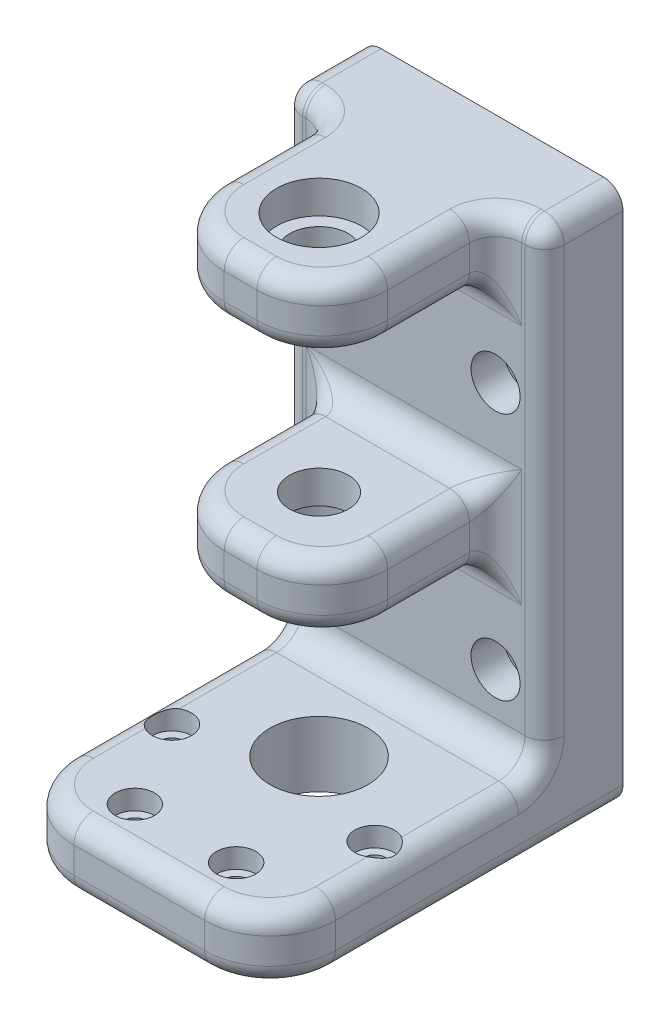
SolidWorks part; units mm, degrees
note: The reader was unsure of these and kept them because the rebuilt part matched: shared geometry of "Croquis3<2>".
ref_plane "Alzado" through (0, 0, 0) normal (1, 0, 0) x (0, 1, 0)
ref_plane "Planta" through (0, 0, 0) normal (0, 0, 1) x (0, 1, 0)
ref_plane "Vista lateral" through (0, 0, 0) normal (0, 1, 0) x (-1, 0, 0)
sketch "Croquis1" plane through (0, 0, 0) normal (0, 1, 0) x (-1, 0, 0)
  line L0 (-12.5, -14.5) -> (-20, -14.5)
  line L2 (-12.5, -14.5) -> (-12.5, 12)
  line L3 (-12.5, 12) -> (12.5, 12)
  line L4 (12.5, -14.5) -> (12.5, 12)
  line L7 (20, -14.5) -> (12.5, -14.5)
  line L8 (20, -14.5) -> (20, -26.5)
  line L9 (20, -26.5) -> (-20, -26.5)
  line L10 (-20, -14.5) -> (-20, -26.5)
  line L11 (0, 0) -> (0, -26.5) construction
  circle A0 centre (0, 0) radius 4.5
  circle A1 centre (0, 0) radius 4.05 construction
  point P0 (0, 0)
  point P16 (0, 12)
  dimension "D3" = 9
  dimension "D1" = 25
  dimension "D5" = 12
  dimension "D6" = 40
  dimension "D2" = 26.5
  dimension "D4" = 12
extrude "Saliente-Extruir1" add sketch "Croquis1" along normal mid plane 47
sketch "Croquis2" plane through (0, 0, 12) normal (0, 0, 1) x (1, 0, 0)
  line L0 (12.5, 23.5) -> (12.5, -23.5) construction
  line L1 (12.5, 13.5) -> (-12.5, 13.5)
  line L2 (12.5, 13.5) -> (12.5, -13.5)
  line L3 (12.5, -13.5) -> (-12.5, -13.5)
  line L4 (-12.5, 13.5) -> (-12.5, -13.5)
  line L5 (-12.5, 23.5) -> (-12.5, -23.5) construction
  line L8 (-12.5, -23.5) -> (12.5, -23.5) construction
  line L9 (-12.5, 23.5) -> (12.5, 23.5) construction
  dimension "D1" = 10
  dimension "D2" = 10
extrude "Cortar-Extruir1" cut sketch "Croquis2" against normal up to surface (26.5 mm away) up to face at (-16.25, 0, -14.5)
fillet "Redondeo1" radius 10 4 edges at (-12.5, 18.5, 12) (12.5, 18.5, 12) (-12.5, -18.5, 12) (12.5, -18.5, 12)
sketch "Croquis3" plane through (0, 0, 0) normal (0, 1, 0) x (-1, 0, 0)
  circle A0 centre (0, 0) radius 6.5
  dimension "D1" = 13
extrude "Cortar-Extruir2" cut sketch "Croquis3" along normal blind 5 from surface at -23.5 starting at face at (0, -23.5, -7.8858)
sketch "Croquis4" plane through (0, 0, -14.5) normal (0, 0, 1) x (0, 1, 0)
  line L0 (0, 12.5) -> (0, -12.5) construction
  line L2 (0, 12.5) -> (-38, 12.5) construction
  line L4 (-13.5, 12.5) -> (-23.5, 12.5) construction
  line L7 (-38, 12.5) -> (-38, -12.5) construction
  point P1 (0, -12.5)
  point P20 (-38, 12.5)
  point P23 (0, 12.5)
  point P37 (-38, -12.5)
  dimension "D1" = 0
  dimension "D3" = 38
extrude "Cortar-Extruir3" cut sketch "Croquis3<2>" against normal blind 5 from surface at 23.5 starting at face at (0, 23.5, -7.8858)
sketch "Croquis3<2>" plane through (0, 0, 0) normal (0, 1, 0) x (-1, 0, 0) same geometry as "Croquis3"
sketch "Croquis6" plane through (0, -23.5, 0) normal (0, -1, 0) x (1, 0, 0)
  line L1 (-20, -14.5) -> (20, -14.5)
  line L2 (-20, -14.5) -> (-20, -26.5)
  line L3 (-20, -26.5) -> (20, -26.5)
  line L4 (20, -14.5) -> (20, -26.5)
extrude "Saliente-Extruir2" add sketch "Croquis6" along normal blind 25
sketch "Croquis7" plane through (0, -48.5, 0) normal (0, -1, 0) x (1, 0, 0)
  line L0 (20, -26.5) -> (20, -14.5) construction
  line L1 (-20, -26.5) -> (20, -26.5)
  line L2 (-20, -26.5) -> (-20, 17.5)
  line L3 (-10, 27.5) -> (10, 27.5)
  line L4 (20, -26.5) -> (20, 17.5)
  line L5 (0, 7) -> (15.5, 7) construction
  line L6 (0, 7) -> (7.75, 20.4234) construction
  arc A0 (10, 27.5) -> (20, 17.5) centre (10, 17.5) cw
  arc A1 (-20, 17.5) -> (-10, 27.5) centre (-10, 17.5) cw
  circle A3 centre (0, 7) radius 15.5 construction
  circle A4 centre (0, 0) radius 7.5
  point P9 (20, 27.5)
  point P14 (0, 0)
  point P16 (15.5, 7)
  point P20 (7.75, 20.4234)
  point P21 (-7.75, 20.4234)
  point P22 (-15.5, 7)
  dimension "D2" = 10
  dimension "D3" = 7
  dimension "D4" = 31
  dimension "D7" = 15
  dimension "D1" = 54
  dimension "D6" = 60
  dimension "D5" = 4
extrude "Saliente-Extruir3" add sketch "Croquis7" along normal blind 10
sketch "Croquis8" plane through (0, -48.5, 0) normal (0, -1, 0) x (1, 0, 0)
  point P0 (15.5, 7)
  point P2 (7.75, 20.4234)
  point P4 (-7.75, 20.4234)
  point P6 (-15.5, 7)
hole_wizard "Refrentado para tornillo con cabeza troncocónica de M32" positions "Croquis8" profile "Croquis9" counterbore size "M3" standard "Ansi Metric" end condition up to next
sketch "Croquis9" plane through (15.5, -48.5, 7) normal (1, 0, 0) x (0, 0, 1)
  line L0 (0, 0) -> (0, 10)
  line L1 (0, 10) -> (1.7, 10)
  line L3 (1.7, 10) -> (1.7, 3)
  line L4 (1.7, 3) -> (3, 3)
  line L5 (3, 3) -> (3, 0)
  line L7 (3, 0) -> (0, 0)
  line L11 (0, -6.35) -> (0, 107.95) construction
  dimension "Diámetro de taladro hasta el siguiente" = 3.4
  dimension "Profundidad de taladro hasta el siguiente" = 10
  dimension "Diámetro de refrentado" = 6
  dimension "Profundidad de refrentado" = 3
hole_wizard "Refrentado para tornillo con cabeza troncocónica de M41" positions "Croquis4" profile "Croquis5" counterbore size "M4" standard "Ansi Metric"
sketch "Croquis5" plane through (12.5, 0, -14.5) normal (1, 0, 0) x (0, -1, 0)
  line L0 (0, 0) -> (0, 16.3519)
  line L1 (0, 16.3519) -> (2.25, 15)
  line L2 (2.25, 15) -> (2.25, 5)
  line L3 (2.25, 5) -> (3.75, 5)
  line L4 (3.75, 5) -> (3.75, 0)
  line L5 (3.75, 0) -> (0, 0)
  line L10 (0, 16.3519) -> (-2.25, 15) construction
  line L11 (0, -6.35) -> (0, 107.95) construction
  dimension "Diámetro de taladro" = 4.5
  dimension "Profundidad de taladro" = 15
  dimension "Diámetro de refrentado" = 7.5
  dimension "Profundidad de refrentado" = 5
  dimension "Ángulo de perforador" = 118
fillet "Redondeo3" radius 4 8 edges at (0, 13.5, -14.5) (0, -23.5, -14.5) (0, -13.5, -14.5) (0, -48.5, -14.5) (-12.5, -18.5, -14.5) (-12.5, 18.5, -14.5) (12.5, 18.5, -14.5) (12.5, -18.5, -14.5)
fillet "Redondeo4" radius 3 46 edges at (20, -58.5, -4.5) (17.0711, -58.5, 24.5711) (0, -58.5, 27.5) (-17.0711, -58.5, 24.5711) (-18.25, 23.5, -14.5) (-13.6716, 23.5, -13.3284) (-12.5, 23.5, -4.25) (-9.5711, 23.5, 9.0711) (0, 23.5, 12) (9.5711, 23.5, 9.0711) (18.25, 23.5, -14.5) (13.6716, 23.5, -13.3284) (13.6716, 12.3284, -13.3284) (-13.6716, 12.3284, -13.3284) (-12.5, 13.5, -4.25) (-9.5711, 13.5, 9.0711) (0, 13.5, 12) (9.5711, 13.5, 9.0711) (-13.6716, -24.6716, -13.3284) (-12.5, -23.5, -4.25) (-9.5711, -23.5, 9.0711) (0, -23.5, 12) (9.5711, -23.5, 9.0711) (13.6716, -24.6716, -13.3284) (13.6716, -12.3284, -13.3284) (-13.6716, -12.3284, -13.3284) (-12.5, -13.5, -4.25) (-9.5711, -13.5, 9.0711) (0, -13.5, 12) (9.5711, -13.5, 9.0711) (20, -10.5, -14.5) (20, -47.3284, -13.3284) (-20, -10.5, -14.5) (-20, -47.3284, -13.3284) (-20, -48.5, 3.5) (-17.0711, -48.5, 24.5711) (0, -48.5, 27.5) (17.0711, -48.5, 24.5711) (-20, -58.5, -4.5) (-20, 23.5, -20.5) (20, 23.5, -20.5) (12.5, 23.5, -4.25) (12.5, 13.5, -4.25) (12.5, -23.5, -4.25) (12.5, -13.5, -4.25) (20, -48.5, 3.5)
equation "\"ancho\"= 25"
equation "\"D1@Croquis1\"=\"ancho\""
equation "\"altura_total\"=30"
equation "\"altura_eje_motor\"=26.5"
equation "\"d_eje_motor\"=9"
equation "\"D3@Croquis1\"=\"d_eje_motor\""
equation "\"esp\"=10"
equation "\"D1@Saliente-Extruir1\"=\"esp\"*2+\"ancho_polea\"+\"sep_polea\"*2"
equation "\"D1\"= \"esp\""
equation "\"D1@Croquis2\"=\"esp\""
equation "\"D2@Croquis2\"=\"D1@Croquis2\""
equation "\"D6@Croquis1\"=\"D1@Croquis1\"+15"
equation "\"d_rodamiento\"=13"
equation "\"D1@Croquis3\"=\"d_rodamiento\""
equation "\"ancho_polea\"= 21"
equation "\"sep_polea\"= 3"
equation "\"sep_acople\"=25"
equation "\"D1@Saliente-Extruir2\"=\"sep_acople\""
equation "\"esp_sop_motor\"=10"
equation "\"D1@Saliente-Extruir3\"=\"esp_sop_motor\""
equation "\"D2@Croquis1\"=\"altura_eje_motor\""
